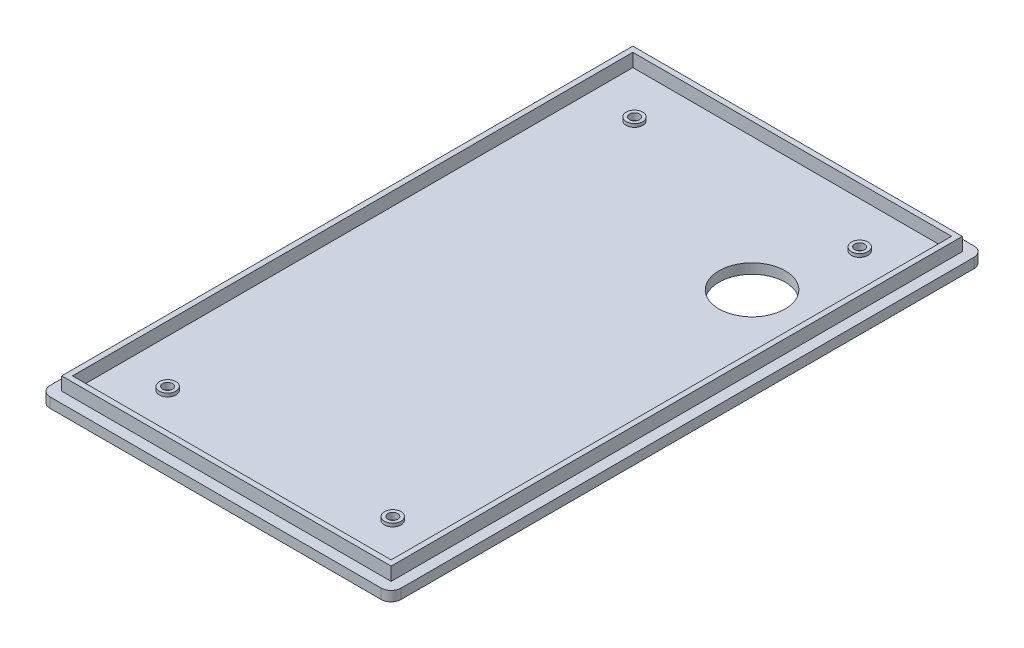
SolidWorks part; units mm, degrees
ref_plane "Alzado" through (0, 0, 0) normal (0, 0, 1) x (1, 0, 0)
ref_plane "Planta" through (0, 0, 0) normal (0, 1, 0) x (1, 0, 0)
ref_plane "Vista lateral" through (0, 0, 0) normal (1, 0, 0) x (0, 0, -1)
sketch "Croquis3" plane through (0, 0, 0) normal (0, 1, 0) x (1, 0, 0)
  line L0 (49.75, 86.25) -> (-49.75, 86.25)
  line L1 (-53, 89.5) -> (53, 89.5)
  line L2 (-53, 89.5) -> (-53, -89.5)
  line L3 (-53, -89.5) -> (53, -89.5)
  line L4 (53, 89.5) -> (53, -89.5)
  line L5 (-53, 89.5) -> (53, -89.5) construction
  line L6 (-53, -89.5) -> (53, 89.5) construction
  line L7 (-49.75, 86.25) -> (-49.75, -86.25)
  line L8 (-49.75, -86.25) -> (49.75, -86.25)
  line L9 (49.75, -86.25) -> (49.75, 86.25)
  line L14 (-48.125, 84.625) -> (48.125, 84.625)
  line L15 (48.125, 84.625) -> (48.125, -84.625)
  line L16 (48.125, -84.625) -> (-48.125, -84.625)
  line L17 (-48.125, -84.625) -> (-48.125, 84.625)
  point P0 (0, 0)
  dimension "D1" = 179
  dimension "D2" = 106
  dimension "D3" = 99.5
  dimension "D4" = 172.5
  dimension "D5" = 1.625
  dimension "D6" = 1.625
  dimension "D7" = 1.625
  dimension "D8" = 1.625
  dimension "D9" = 3.25
  dimension "D10" = 3.25
extrude "Saliente-Extruir4" add sketch "Croquis3" along normal blind 3 contours L16 L15 | L8 L9 L0 L7 L16 L15 | L4 L1 L2 L3 L9 L8 L7 L0 region at (49.5509, 0, 0) region at (0, 0, -87.4197) region at (0, 0, 0)
sketch "Croquis6" plane through (0, 3, 0) normal (0, 1, 0) x (1, 0, 0)
extrude "Saliente-Extruir5" add sketch "Croquis3<6>" along normal blind 7 contours L8 L9 L0 L7 L16 L15 region at (49.5509, 0, 0)
sketch "Croquis3<6>" plane through (0, 0, 0) normal (0, 1, 0) x (1, 0, 0) same geometry as "Croquis3"
sketch "Croquis7" plane through (0, 0, 0) normal (0, -1, 0) x (1, 0, 0)
  line L2 (-53, -89.5) -> (53, -89.5) construction
  line L3 (53, -89.5) -> (53, 89.5) construction
  circle A0 centre (28, -44.5) radius 10
  dimension "D1" = 20
  dimension "D2" = 45
  dimension "D3" = 25
extrude "Cortar-Extruir1" cut sketch "Croquis7" against normal blind 7
fillet "Redondeo1" radius 3 4 edges at (53, 1.5, -89.5) (-53, 1.5, -89.5) (53, 1.5, 89.5) (-53, 1.5, 89.5)
sketch "Croquis8" plane through (0, 3, 0) normal (0, 1, 0) x (1, 0, 0)
  line L0 (-53, 86.5) -> (-53, -86.5) construction
  line L2 (-50, 89.5) -> (50, 89.5) construction
  line L5 (53, 86.5) -> (53, -86.5) construction
  line L6 (-50, -89.5) -> (50, -89.5) construction
  circle A0 centre (-34, 71) radius 1.5
  circle A1 centre (34, 71) radius 1.5
  circle A2 centre (-34, -70) radius 1.5
  circle A3 centre (34, -70) radius 1.5
  dimension "D1" = 19
  dimension "D5" = 3
  dimension "D6" = 3
  dimension "D7" = 3
  dimension "D8" = 3
  dimension "D9" = 19.5
  dimension "D10" = 19
  dimension "D12" = 19
  dimension "D2" = 18.5
  dimension "D3" = 18.5
  dimension "D4" = 19
  dimension "D11" = 19.5
extrude "Cortar-Extruir2" cut sketch "Croquis8" against normal blind 20 and the other way blind 20
sketch "Croquis12" plane through (0, 0, 0) normal (0, -1, 0) x (1, 0, 0)
  circle A0 centre (-34, 70) radius 3
  circle A1 centre (34, 70) radius 3
  circle A2 centre (34, -71) radius 3
  circle A3 centre (-34, -71) radius 3
extrude "Cortar-Extruir3" cut sketch "Croquis12" against normal blind 2
sketch "Croquis13" plane through (0, 3, 0) normal (0, 1, 0) x (1, 0, 0)
  circle A0 centre (-34, 71) radius 2.5
  circle A1 centre (34, 71) radius 2.5
  circle A3 centre (-34, -70) radius 2.5
  circle A4 centre (34, -70) radius 2.5
extrude "Saliente-Extruir7" add sketch "Croquis13" along normal blind 1
sketch "Croquis14" plane through (0, 0, 0) normal (0, -1, 0) x (1, 0, 0)
  circle A0 centre (-34, 70) radius 1.5
  circle A1 centre (34, 70) radius 1.5
  circle A2 centre (34, -71) radius 1.5
  circle A3 centre (-34, -71) radius 1.5
extrude "Cortar-Extruir4" cut sketch "Croquis14" against normal blind 11 and the other way blind 1
